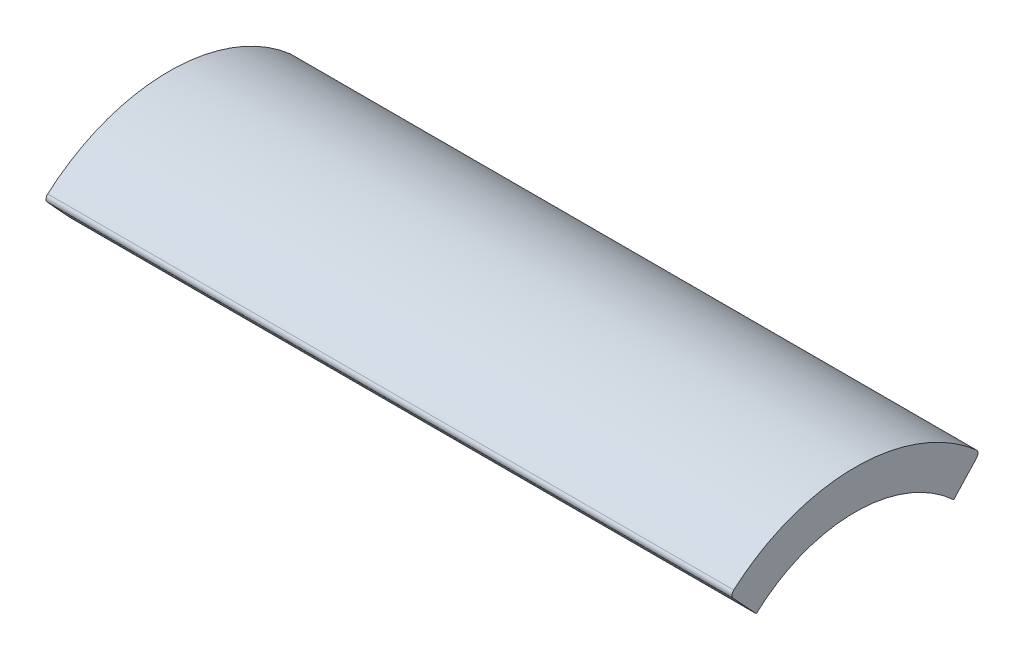
SolidWorks part; units mm, degrees
material "Vacodym 131 DTP"
ref_plane "Front Plane" through (0, 0, 0) normal (0, 0, 1) x (1, 0, 0)
ref_plane "Top Plane" through (0, 0, 0) normal (0, 1, 0) x (1, 0, 0)
ref_plane "Right Plane" through (0, 0, 0) normal (1, 0, 0) x (0, 0, -1)
ref_axis "Axis1" through (88.99, 0, 0) along (-1, 0, 0)
sketch "Sketch1" plane through (0, 0, 0) normal (1, 0, 0) x (0, 0, -1)
  line L0 (0, 0) -> (0, 9.4) construction
  line L1 (-6.2087, 6.7165) -> (-5.0367, 5.4487)
  line L2 (6.2087, 6.7165) -> (5.0367, 5.4487)
  arc A0 (-6.1897, 7.0744) -> (6.1897, 7.0744) centre (0, 0) cw
  arc A1 (-5.0367, 5.4487) -> (5.0367, 5.4487) centre (0, 0) cw
  arc A2 (6.2087, 6.7165) -> (6.1897, 7.0744) centre (6.0251, 6.8862) ccw
  arc A3 (-6.1897, 7.0744) -> (-6.2087, 6.7165) centre (-6.0251, 6.8862) ccw
  point P11 (6.3807, 6.9026)
  point P14 (-6.3807, 6.9026)
  dimension "D2" = 7.42
  dimension "D4" = 0.25
  dimension "D1" = 85.5
  dimension "D3" = 1.98
extrude "Boss-Extrude1" add sketch "Sketch1" along normal mid plane 35 contours A0 A2 L2 A1 L1 A3
equation "\"ppairs\"= 2"
equation "\"pcoverage\"= 0.95"
equation "\"tmag\"= 1.98"
equation "\"Di\"= 14.84"
equation "\"D2@Sketch1\"=\"Di\"/2"
equation "\"D3@Sketch1\"=\"tmag\""
equation "\"D1@Sketch1\"=\"pcoverage\"*360deg / \"ppairs\"/2"
equation "\"length\"= 35mm"
equation "\"D1@Boss-Extrude1\"=\"length\""
